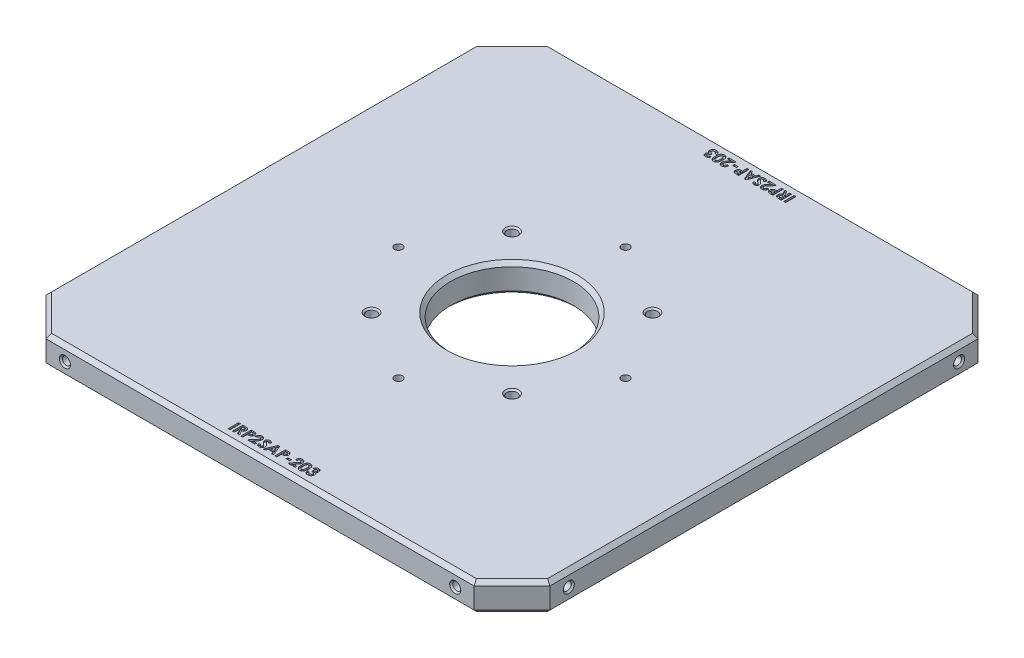
SolidWorks part; units mm, degrees
material "6061-T6 (SS)"
ref_plane "Front" through (0, 0, 0) normal (0, 0, 1) x (1, 0, 0)
ref_plane "Top" through (0, 0, 0) normal (0, 1, 0) x (1, 0, 0)
ref_plane "Right" through (0, 0, 0) normal (1, 0, 0) x (0, 0, -1)
sketch "Sketch1" plane through (0, 0, 0) normal (0, 1, 0) x (1, 0, 0)
  line L1 (-84.5344, -84.5344) -> (84.5344, -84.5344)
  line L2 (-84.5344, -84.5344) -> (-84.5344, 84.5344)
  line L3 (-84.5344, 84.5344) -> (84.5344, 84.5344)
  line L4 (84.5344, -84.5344) -> (84.5344, 84.5344)
  line L5 (-84.5344, -84.5344) -> (84.5344, 84.5344) construction
  line L6 (-84.5344, 84.5344) -> (84.5344, -84.5344) construction
  line L7 (23.5712, -23.5712) -> (-23.5712, -23.5712) construction
  line L8 (23.5712, -23.5712) -> (23.5712, 23.5712) construction
  line L9 (23.5712, 23.5712) -> (-23.5712, 23.5712) construction
  line L10 (-23.5712, -23.5712) -> (-23.5712, 23.5712) construction
  line L11 (23.5712, -23.5712) -> (-23.5712, 23.5712) construction
  line L12 (23.5712, 23.5712) -> (-23.5712, -23.5712) construction
  circle A0 centre (0, 0) radius 20.6375
  circle A1 centre (-23.5712, 23.5712) radius 3.175 construction
  circle A2 centre (23.5712, 23.5712) radius 3.175 construction
  circle A3 centre (23.5712, -23.5712) radius 3.175 construction
  circle A4 centre (-23.5712, -23.5712) radius 3.175 construction
  point P0 (0, 0)
  dimension "D4" = 41.275
  dimension "D5" = 6.35
  dimension "D1" = 169.0687
  dimension "D3" = 47.1424
extrude "Boss-Extrude1" add sketch "Sketch1" along normal blind 9.525
chamfer "Chamfer1" distance 12.7 angle 45 4 edges at (-84.5344, 4.7625, -84.5344) (84.5344, 4.7625, -84.5344) (84.5344, 4.7625, 84.5344) (-84.5344, 4.7625, 84.5344)
hole_wizard "#6-32 Tapped Hole1" positions "Sketch3" profile "Sketch4" tap size "#6-32" standard "ANSI Inch"
sketch "Sketch3" plane through (0, 0, 84.5344) normal (0, 0, 1) x (1, 0, 0)
  line L0 (-71.8344, 4.7625) -> (-65.4844, 4.7625) construction
  line L1 (-71.8344, 9.525) -> (-71.8344, 0) construction
  line L2 (-65.4844, 4.7625) -> (65.4844, 4.7625) construction
  line L3 (65.4844, 4.7625) -> (71.8344, 4.7625) construction
  line L4 (71.8344, 0) -> (71.8344, 9.525) construction
  point P0 (-65.4844, 4.7625)
  point P2 (65.4844, 4.7625)
  dimension "D1" = 130.9688
sketch "Sketch4" plane through (-65.4844, 4.7625, 84.5344) normal (1, 0, 0) x (0, -1, 0)
  line L0 (0, 0) -> (0, 16.6877)
  line L1 (0, 16.6877) -> (1.3525, 15.875)
  line L2 (1.3525, 15.875) -> (1.3525, 0)
  line L5 (1.3525, 0) -> (0, 0)
  line L10 (0, 16.6877) -> (-1.3526, 15.875) construction
  line L11 (0, -6.35) -> (0, 107.95) construction
  dimension "Tap Drill Dia." = 2.7051
  dimension "Tap Drill Depth" = 15.875
  dimension "Drill Angle" = 118
cosmetic thread "Hole Thread1" parameters "D1"=15.0825, "D2"=3.5052
cosmetic thread "Hole Thread2" parameters "D1"=15.0825, "D2"=3.5052
pattern_circular "CirPattern1" count 4 over 360 about axis through (0, 9.525, 0) along (0, 1, 0) of "#6-32 Tapped Hole1"
cosmetic thread "Hole Thread3" parameters "D1"=15.0825, "D2"=3.5052
cosmetic thread "Hole Thread4" parameters "D1"=15.0825, "D2"=3.5052
cosmetic thread "Hole Thread5" parameters "D1"=15.0825, "D2"=3.5052
cosmetic thread "Hole Thread6" parameters "D1"=15.0825, "D2"=3.5052
cosmetic thread "Hole Thread11" parameters "D1"=15.0825, "D2"=3.5052
cosmetic thread "Hole Thread12" parameters "D1"=15.0825, "D2"=3.5052
hole_wizard "#8-32 Tapped Hole2" positions "Sketch5" profile "Sketch6" tap size "#8-32" standard "ANSI Inch" end condition through all
sketch "Sketch5" plane through (0, 9.525, 0) normal (0, 1, 0) x (1, 0, 0)
  point P0 (-23.5712, 23.5712)
  point P2 (23.5712, 23.5712)
  point P4 (23.5712, -23.5712)
  point P6 (-23.5712, -23.5712)
sketch "Sketch6" plane through (-23.5712, 9.525, -23.5712) normal (1, 0, 0) x (0, 0, 1)
  line L0 (0, 0) -> (0, 9.525)
  line L1 (0, 9.525) -> (1.7272, 9.525)
  line L2 (1.7272, 9.525) -> (1.7272, 0)
  line L5 (1.7272, 0) -> (0, 0)
  line L11 (0, -6.35) -> (0, 107.95) construction
  dimension "Thru Tap Drill Dia." = 3.4544
  dimension "Thru Tap Drill Depth" = 9.525
cosmetic thread "Hole Thread7" parameters "D2"=4.1656
cosmetic thread "Hole Thread8" parameters "D2"=4.1656
cosmetic thread "Hole Thread9" parameters "D2"=4.1656
cosmetic thread "Hole Thread10" parameters "D2"=4.1656
chamfer "Chamfer2" distance 0.508 angle 45 16 edges at (-84.5344, 4.7625, 66.8369) (-84.5344, 4.7625, -64.1318) (-66.8369, 4.7625, -84.5344) (64.1318, 4.7625, -84.5344) (84.5344, 4.7625, -66.8369) (-64.1318, 4.7625, 84.5344) (84.5344, 4.7625, 64.1318) (66.8369, 4.7625, 84.5344) (-23.5712, 9.525, 25.2984) (-23.5712, 0, 25.2984) (23.5712, 9.525, 25.2984) (23.5712, 0, 25.2984) (23.5712, 9.525, -21.844) (23.5712, 0, -21.844) (-23.5712, 9.525, -21.844) (-23.5712, 0, -21.844)
chamfer "Chamfer3" distance 1.27 angle 45 18 edges at (0, 0, 20.6375) (-78.1844, 0, 78.1844) (0, 0, 84.5344) (78.1844, 0, 78.1844) (84.5344, 0, 0) (78.1844, 0, -78.1844) (0, 0, -84.5344) (-78.1844, 0, -78.1844) (-84.5344, 0, 0) (0, 9.525, 20.6375) (78.1844, 9.525, -78.1844) (84.5344, 9.525, 0) (78.1844, 9.525, 78.1844) (0, 9.525, 84.5344) (-78.1844, 9.525, 78.1844) (-84.5344, 9.525, 0) (-78.1844, 9.525, -78.1844) (0, 9.525, -84.5344)
sketch "Sketch7" plane through (0, 0, 0) normal (0, -1, 0) x (1, 0, 0)
  line L0 (-83.2644, 81.3594) -> (83.2644, 81.3594) construction
  line L1 (-83.2644, 71.3083) -> (-83.2644, -71.3083) construction
  line L2 (83.2644, -71.3083) -> (83.2644, 71.3083) construction
  line L3 (-83.2644, -81.3594) -> (84.5344, -81.3594) construction
  line L4 (84.5344, 71.8344) -> (84.5344, -71.8344) construction
  line L5 (-71.8344, 84.5344) -> (71.8344, 84.5344) construction
  line L6 (71.8344, -84.5344) -> (-71.8344, -84.5344) construction
  text T0 "<b>IRP2SAP-203</b>"
  text T1 "<b>IRP2SAP-203</b>"
  dimension "D1" = 3.175
  dimension "D2" = 3.175
extrude "Cut-Extrude1" cut sketch "Sketch7" against normal blind 0.508
sketch "Sketch8" plane through (0, 9.525, 0) normal (0, 1, 0) x (1, 0, 0)
  line L0 (-84.5344, 81.3594) -> (84.5344, 81.3594) construction
  line L1 (-84.5344, -71.8344) -> (-84.5344, 71.8344) construction
  line L2 (84.5344, 71.8344) -> (84.5344, -71.8344) construction
  line L3 (-84.5344, -81.3594) -> (84.5344, -81.3594) construction
  line L4 (-71.8344, 84.5344) -> (71.8344, 84.5344) construction
  line L5 (71.8344, -84.5344) -> (-71.8344, -84.5344) construction
  text T0 "<b>IRP2SAP-203</b>"
  text T1 "<b>IRP2SAP-203</b>"
  dimension "D1" = 3.175
  dimension "D2" = 3.175
extrude "Cut-Extrude2" cut sketch "Sketch8" against normal blind 0.508
hole_wizard "#6-32 Tapped Hole2" positions "Sketch9" profile "Sketch10" tap size "#6-32" standard "ANSI Inch" end condition through all
sketch "Sketch9" plane through (0, 0, 0) normal (0, -1, 0) x (-1, 0, 0)
  line L0 (0, -38.1) -> (-38.1, 0) construction
  line L1 (-38.1, 0) -> (0, 38.1) construction
  line L2 (0, 38.1) -> (38.1, 0) construction
  line L3 (38.1, 0) -> (0, -38.1) construction
  line L4 (0, -38.1) -> (0, 38.1) construction
  point P0 (-38.1, 0)
  point P2 (0, 38.1)
  point P4 (0, -38.1)
  point P6 (38.1, 0)
  dimension "D1" = 76.2
sketch "Sketch10" plane through (38.1, 0, 0) normal (1, 0, 0) x (0, 0, -1)
  line L0 (0, 0) -> (0, 9.525)
  line L1 (0, 9.525) -> (1.3525, 9.525)
  line L2 (1.3525, 9.525) -> (1.3525, 0)
  line L5 (1.3525, 0) -> (0, 0)
  line L11 (0, -6.35) -> (0, 107.95) construction
  dimension "Thru Tap Drill Dia." = 2.7051
  dimension "Thru Tap Drill Depth" = 9.525
cosmetic thread "Hole Thread13" parameters "D2"=3.5052
cosmetic thread "Hole Thread14" parameters "D2"=3.5052
cosmetic thread "Hole Thread15" parameters "D2"=3.5052
cosmetic thread "Hole Thread16" parameters "D2"=3.5052
